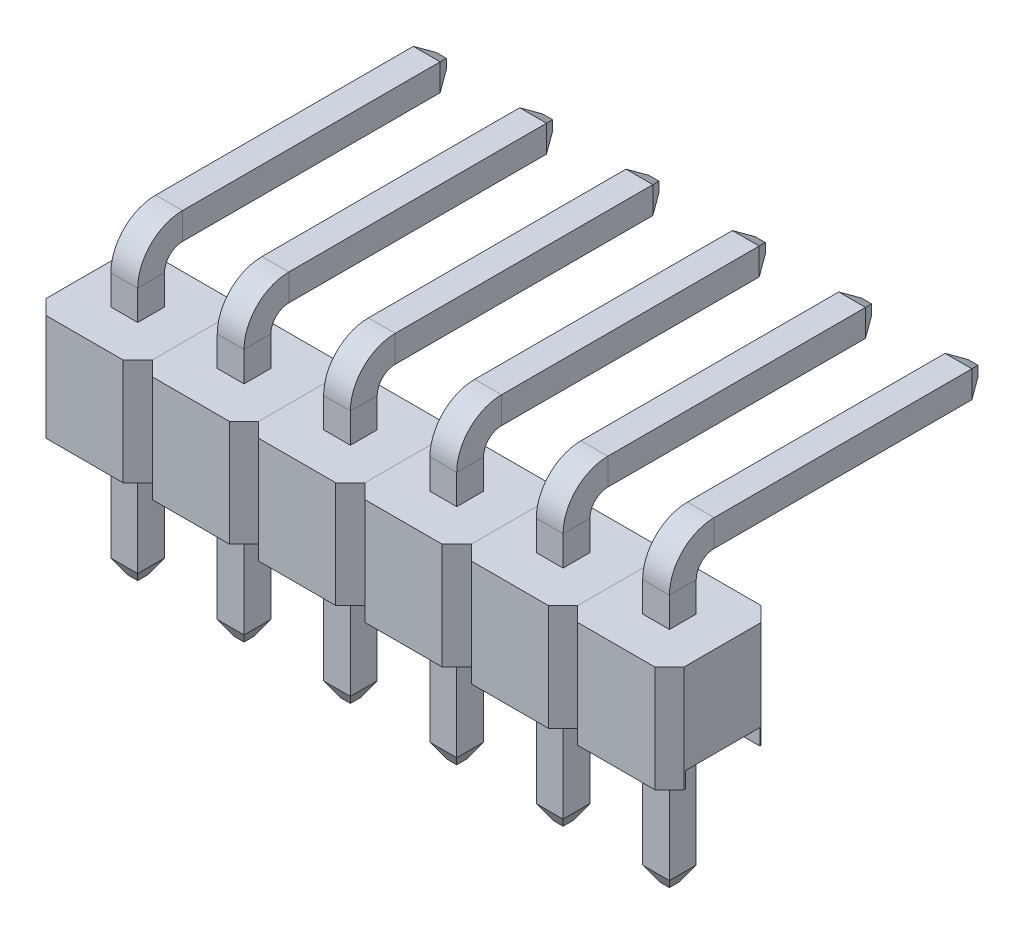
SolidWorks part; units mm, degrees
ref_plane "Front Plane" through (0, 0, 0) normal (0, 0, 1) x (1, 0, 0)
ref_plane "Top Plane" through (0, 0, 0) normal (0, 1, 0) x (1, 0, 0)
ref_plane "Right Plane" through (0, 0, 0) normal (1, 0, 0) x (0, 0, -1)
sketch "Sketch1" plane through (0, 0, 0) normal (0, 1, 0) x (1, 0, 0)
  line L1 (-1.27, -1.27) -> (1.27, -1.27)
  line L2 (-1.27, -1.27) -> (-1.27, 1.27)
  line L3 (-1.27, 1.27) -> (1.27, 1.27)
  line L4 (1.27, -1.27) -> (1.27, 1.27)
  point P5 (0, -1.27)
  point P8 (-1.27, 0)
  dimension "D1" = 2.54
  dimension "D2" = 2.54
extrude "plastic_housing" add sketch "Sketch1" along normal blind 2.54
sketch "Sketch3" plane through (-1.27, 0, 0) normal (-1, 0, 0) x (0, 0, 1)
  line L0 (-1.27, 0) -> (1.27, 0) construction
  line L1 (-0.889, 0) -> (0.889, 0)
  line L2 (-0.889, 0) -> (-0.889, 0.381)
  line L3 (-0.889, 0.381) -> (0.889, 0.381)
  line L4 (0.889, 0) -> (0.889, 0.381)
  line L5 (-1.27, 0) -> (-0.889, 0) construction
  line L6 (0.889, 0) -> (1.27, 0) construction
  dimension "D1" = 0.381
extrude "cut groove" cut sketch "Sketch3" against normal through all
sketch "SKETCH TOP POINT" plane through (0, 2.54, 0) normal (0, 1, 0) x (1, 0, 0)
  line L0 (0, 0) -> (1.27, 1.27) construction
  point P4 (0.635, 0.635)
ref_axis "Axis1" through (0, -0.127, 0) along (0, 1, 0)
chamfer "chamf_housing" distance 0.35 angle 45 4 edges at (1.27, 1.27, 1.27) (1.27, 1.27, -1.27) (-1.27, 1.27, -1.27) (-1.27, 1.27, 1.27)
sketch "Sketch2" plane through (0, 2.54, 0) normal (0, 1, 0) x (1, 0, 0)
  line L0 (0, 1.27) -> (0, 0.32) construction
  line L1 (-0.32, -0.32) -> (0.32, -0.32)
  line L2 (-0.32, -0.32) -> (-0.32, 0.32)
  line L3 (-0.32, 0.32) -> (0.32, 0.32)
  line L4 (0.32, -0.32) -> (0.32, 0.32)
  line L6 (0.92, 1.27) -> (-0.92, 1.27) construction
  line L8 (0, -0.32) -> (0, -1.27) construction
  line L9 (-0.92, -1.27) -> (0.92, -1.27) construction
  dimension "D1" = 0.64
sketch "Sketch5" plane through (0, 0, 0) normal (1, 0, 0) x (0, 0, -1)
  line L0 (0, 0) -> (0, 3.25)
  line L1 (0, 4) -> (0.75, 4) construction
  line L2 (0.75, 4) -> (7.25, 4)
  line L3 (0, 4) -> (0, 3.25) construction
  line L4 (0, 0) -> (0, -3)
  arc A0 (0, 3.25) -> (0.75, 4) centre (0.75, 3.25) cw
  dimension "D3" = 0.75
  dimension "D1" = 4
  dimension "D2" = 7.25
  dimension "D4" = 3
sweep "sweep_pin" add profiles "Sketch2" path "Sketch5"
chamfer "chamf_pin_end" distance 0.2 angle 60 4 edges at (0, 3.68, -7.25) (0.32, 4, -7.25) (0, 4.32, -7.25) (-0.32, 4, -7.25) first distance on face at (0, 4, -7.25)
chamfer "chamf_pin_start" distance 0.2 angle 60 4 edges at (0, -3, 0.32) (0.32, -3, 0) (0, -3, -0.32) (-0.32, -3, 0) first distance on face at (0, -3, 0)
pattern_linear "pattern SLEEVE" count 6 spacing 2.54 along (-1, 0, 0) of "plastic_housing", "cut groove"
pattern_linear "pattern PINS" count 6 spacing 2.54 along (1, 0, 0) of bodies 124 102
equation "\"pins\"= 6"
equation "\"D1@pattern SLEEVE\"=\"pins\""
equation "\"D1@pattern PINS\"=\"pins\""
